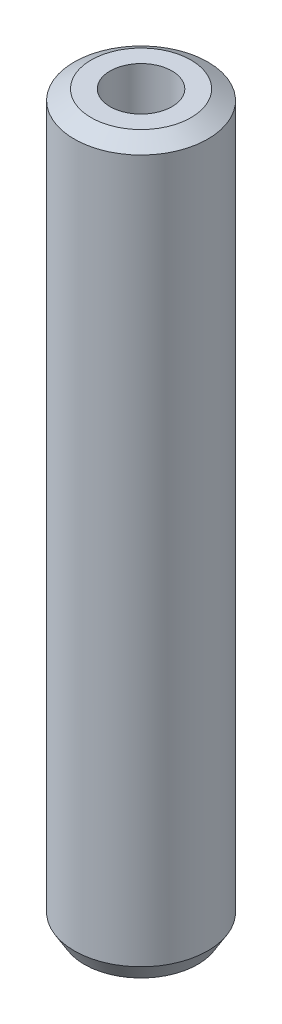
SolidWorks part; units mm, degrees
ref_plane "Front Plane" through (0, 0, 0) normal (0, 0, 1) x (1, 0, 0)
ref_plane "Top Plane" through (0, 0, 0) normal (0, 1, 0) x (1, 0, 0)
ref_plane "Right Plane" through (0, 0, 0) normal (1, 0, 0) x (0, 0, -1)
sketch "Sketch1" plane through (0, 0, 0) normal (0, 1, 0) x (1, 0, 0)
  circle A0 centre (0, 0) radius 7.5
  dimension "SHAFT_OD" = 15
extrude "Boss-Extrude1" add sketch "Sketch1" along normal blind 81.9372
sketch "Sketch2" plane through (0, 0, 0) normal (0, 1, 0) x (1, 0, 0)
  circle A0 centre (0, 0) radius 3.4756
  dimension "BORE_D" = 6.9513
extrude "Cut-Extrude1" cut sketch "Sketch2" along normal through all
chamfer "Chamfer1" distance 1.1362 angle 59.054 2 edges at (0, 81.9372, 7.5) (0, 0, 7.5) first distance on face at (0, 81.9372, 7.5) first distance on face at (0, 0, 3.4756)
